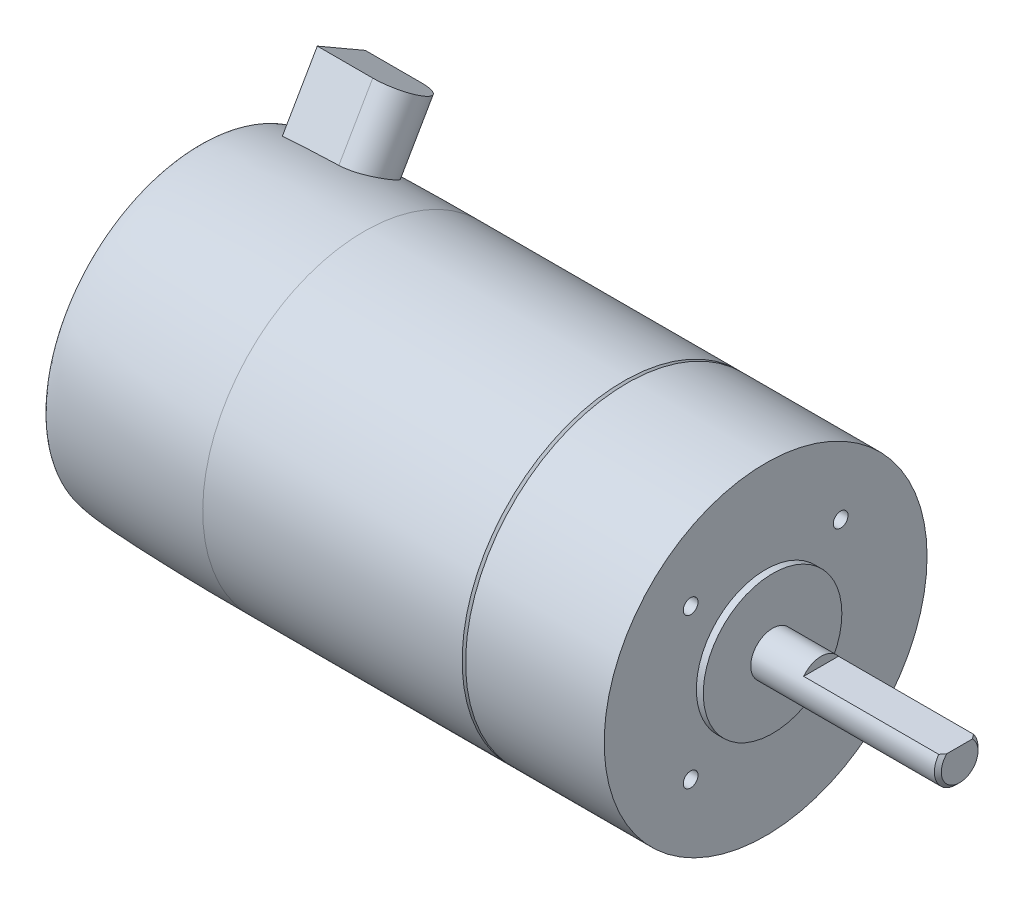
SolidWorks part; units mm, degrees
note: '?' marks a value the reader was unsure of.
material "Massless"
ref_plane "Front Plane" through (0, 0, 0) normal (0, 0, 1) x (1, 0, 0)
ref_plane "Top Plane" through (0, 0, 0) normal (0, 1, 0) x (1, 0, 0)
ref_plane "Right Plane" through (0, 0, 0) normal (1, 0, 0) x (0, 0, -1)
ref_axis "X Axis" through (88.99, 0, 0) along (-1, 0, 0)
ref_axis "Y Axis" through (0, 55, 0) along (0, -1, 0)?
ref_axis "Z Axis" through (0, 0, -88.99) along (0, 0, 1)?
sketch "Sketch2" plane through (0, 0, 0) normal (0, 0, 1) x (1, 0, 0)
  line L0 (35.56, 3.365) -> (34.925, 4) construction
  line L1 (0, -29.591) -> (-103.5558, -29.591) construction
  line L2 (0, -29.591) -> (0, 29.591) construction
  line L3 (0, 29.591) -> (-25.4, 29.591) construction
  line L4 (-103.5558, -29.591) -> (-103.5558, 29.591) construction
  line L5 (35.56, 0) -> (-116.2558, 0)
  line L6 (-116.2558, 0) -> (-116.2558, 4)
  line L7 (-116.2558, -4) -> (-103.5558, -4) construction
  line L8 (-116.2558, -4) -> (-116.2558, 4) construction
  line L9 (-116.2558, 4) -> (-103.5558, 4) construction
  line L10 (-103.5558, -4) -> (-103.5558, 4) construction
  line L11 (-116.2558, 4) -> (-103.5558, 4)
  line L12 (-103.5558, 4) -> (-103.5558, 29.591)
  line L13 (1.27, -12.7) -> (0, -12.7) construction
  line L14 (1.27, -12.7) -> (1.27, 12.7) construction
  line L15 (1.27, 12.7) -> (0, 12.7) construction
  line L16 (0, -12.7) -> (0, 12.7) construction
  line L17 (-103.5558, 29.591) -> (-26.035, 29.591)
  line L19 (35.56, -4) -> (1.27, -4) construction
  line L20 (35.56, -4) -> (35.56, 3.365) construction
  line L21 (34.925, 4) -> (1.27, 4) construction
  line L22 (1.27, -4) -> (1.27, 4) construction
  line L23 (0, 12.7) -> (1.27, 12.7)
  line L24 (1.27, 12.7) -> (1.27, 4)
  line L25 (1.27, 4) -> (34.925, 4)
  line L26 (34.925, 4) -> (35.56, 3.365)
  line L27 (35.56, 3.365) -> (35.56, 0)
  line L28 (0, 29.591) -> (0, 12.7)
  line L29 (-26.035, 29.591) -> (-25.4, 28.956)
  line L30 (-25.4, 28.956) -> (-25.4, 29.591)
  line L31 (-25.4, 29.591) -> (-26.035, 29.591) construction
  line L32 (-26.035, 29.591) -> (-103.5558, 29.591) construction
  line L33 (-26.035, 29.591) -> (-25.4, 29.591) construction
  line L34 (-25.4, 29.591) -> (0, 29.591)
  point P0 (0, 0)
  point P10 (0, 0)
  point P16 (0, 0)
  point P21 (35.56, 4)
  dimension "D1" = 103.5558
  dimension "D2" = 59.182
  dimension "D3" = 8
  dimension "D4" = 12.7
  dimension "D5" = 1.27
  dimension "D6" = 25.4
  dimension "D7" = 35.56
  dimension "D8" = 8
  dimension "D9" = 45
  dimension "D10" = 0.635
  dimension "D12" = 25.4
  dimension "D13" = 4
revolve "Revolve1" add sketch "Sketch2" angle 360 about axis through (88.99, 0, 0) along (-1, 0, 0)
fillet "Fillet1" radius 1.27 1 edges at (-103.5558, 0, -29.591)
sketch "Sketch3" plane through (35.56, 0, 0) normal (1, 0, 0) x (0, 0, -1)
  line L1 (-3.1906, 2.4125) -> (3.1906, 2.4125)
  line L2 (-3.1906, 2.4125) -> (-3.1906, 5.5875)
  line L3 (-3.1906, 5.5875) -> (3.1906, 5.5875)
  line L4 (3.1906, 2.4125) -> (3.1906, 5.5875)
  line L5 (0, 5.5875) -> (0, 2.4125) construction
  line L6 (-3.1906, 4) -> (3.1906, 4) construction
  circle A0 centre (0, 0) radius 4 construction
  point P0 (0, 4)
  dimension "D1" = 3.175
extrude "Cut-Extrude1" cut sketch "Sketch3" against normal blind 25.4
sketch "Sketch4" plane through (0, 0, 0) normal (1, 0, 0) x (0, 0, -1)
  line L0 (0, 0) -> (0, 19.4437) construction
  line L3 (0, 0) -> (19.4437, 0) construction
  line L4 (0, 0) -> (13.7488, 13.7488) construction
  circle A0 centre (0, 0) radius 19.4437 construction
  point P25 (13.7488, 13.7488)
  point P29 (13.7488, -13.7488)
  point P30 (-13.7488, -13.7488)
  point P31 (-13.7488, 13.7488)
  dimension "D1" = 38.8874
  dimension "D2" = 45
  dimension "D3" = 19.4437
  dimension "D4" = 4
hole_wizard "#6-32 Tapped Hole2" positions "Sketch4" profile "Sketch8" tap size "#6-32" standard "ANSI Inch"
sketch "Sketch8" plane through (0, 13.7488, 13.7488) normal (0, 1, 0) x (0, 0, -1)
  line L0 (0, 0) -> (0, 8.8127)
  line L1 (0, 8.8127) -> (1.3525, 8)
  line L2 (1.3525, 8) -> (1.3525, 0)
  line L5 (1.3525, 0) -> (0, 0)
  line L10 (0, 8.8127) -> (-1.3526, 8) construction
  line L11 (0, -6.35) -> (0, 107.95) construction
  dimension "Tap Drill Dia." = 2.7051
  dimension "Tap Drill Depth" = 8
  dimension "Drill Angle" = 118
cosmetic thread "Hole Thread3" parameters "D1"=7.112, "D2"=3.5052
cosmetic thread "Hole Thread12" parameters "D1"=7.112, "D2"=3.5052
cosmetic thread "Hole Thread13" parameters "D1"=7.112, "D2"=3.5052
cosmetic thread "Hole Thread14" parameters "D1"=7.112, "D2"=3.5052
sketch "Sketch6" plane through (-103.5558, 0, 0) normal (-1, 0, 0) x (0, 0, 1)
  line L2 (16.256, 0) -> (-16.256, 0) construction
  line L3 (-11.5062, -19.9293) -> (11.5062, 19.9293) construction
  circle A0 centre (0, 0) radius 16.256 construction
  circle A1 centre (0, 0) radius 23.0124 construction
  point P60 (0, 0)
  point P77 (0, 0)
  point P82 (11.5062, 19.9293)
  point P83 (8.128, 14.0781)
  point P85 (-8.128, -14.0781)
  point P89 (-11.5062, -19.9293)
  dimension "D1" = 32.512
  dimension "D2" = 46.0248
  dimension "D3" = 60
hole_wizard "#6-32 Tapped Hole1" positions "Sketch6" profile "Sketch7" tap size "#6-32" standard "ANSI Inch"
sketch "Sketch7" plane through (-103.5558, -19.9293, -11.5062) normal (0, 1, 0) x (0, 0, 1)
  line L0 (0, 0) -> (0, 10.2107)
  line L1 (0, 10.2107) -> (1.3525, 9.398)
  line L2 (1.3525, 9.398) -> (1.3525, 0)
  line L5 (1.3525, 0) -> (0, 0)
  line L10 (0, 10.2107) -> (-1.3526, 9.398) construction
  line L11 (0, -6.35) -> (0, 107.95) construction
  dimension "Tap Drill Dia." = 2.7051
  dimension "Tap Drill Depth" = 9.398
  dimension "Drill Angle" = 118
cosmetic thread "Hole Thread2" parameters "D1"=7.112, "D2"=3.5052
cosmetic thread "Hole Thread15" parameters "D1"=7.112, "D2"=3.5052
cosmetic thread "Hole Thread16" parameters "D1"=7.112, "D2"=3.5052
cosmetic thread "Hole Thread17" parameters "D1"=7.112, "D2"=3.5052
sketch "Sketch11" plane through (-103.5558, 0, 0) normal (-1, 0, 0) x (0, 0, 1)
  point P0 (-16.256, 0)
  point P3 (16.256, 0)
hole_wizard "#4-40 Tapped Hole1" [suppressed] positions "Sketch11" profile "Sketch10" tap size "#4-40" standard "ANSI Inch"
sketch "Sketch10" plane through (-103.5558, 0, -16.256) normal (0, 1, 0) x (0, 0, 1)
  line L0 (0, 0) -> (0, 8.2992)
  line L1 (0, 8.2992) -> (1.1303, 7.62)
  line L2 (1.1303, 7.62) -> (1.1303, 0)
  line L5 (1.1303, 0) -> (0, 0)
  line L10 (0, 8.2992) -> (-1.1303, 7.62) construction
  line L11 (0, -6.35) -> (0, 107.95) construction
  dimension "Tap Drill Dia." = 2.2606
  dimension "Tap Drill Depth" = 7.62
  dimension "Drill Angle" = 118
cosmetic thread "Hole Thread4" [suppressed] parameters "D1"=5.588, "D2"=2.8448
cosmetic thread "Hole Thread5" [suppressed] parameters "D1"=5.588, "D2"=2.8448
pattern_circular "CirPattern1" count 4 every 90 about axis through (88.99, 0, 0) along (-1, 0, 0) skipping 1, 2, 3 of "#6-32 Tapped Hole1", "#6-32 Tapped Hole2"
cosmetic thread "Hole Thread6" parameters "D1"=7.112, "D2"=3.5052
cosmetic thread "Hole Thread7" parameters "D1"=7.112, "D2"=3.5052
cosmetic thread "Hole Thread8" parameters "D1"=7.112, "D2"=3.5052
cosmetic thread "Hole Thread9" parameters "D1"=7.112, "D2"=3.5052
cosmetic thread "Hole Thread10" parameters "D1"=7.112, "D2"=3.5052
cosmetic thread "Hole Thread11" parameters "D1"=7.112, "D2"=3.5052
ref_plane "Lead Plane" through (0, 0, 0) normal (0, 0.866, -0.5) x (-1, 0, 0)
sketch "Sketch12" plane through (0, 0, 0) normal (0, 0.866, -0.5) x (1, 0, 0)
  line L0 (-103.5558, 29.591) -> (-103.5558, -29.591) construction
  line L1 (-98.4758, -5.08) -> (-88.3158, -5.08)
  line L2 (-98.4758, -5.08) -> (-98.4758, 5.08)
  line L3 (-98.4758, 5.08) -> (-88.3158, 5.08)
  line L6 (-98.4758, 0) -> (-83.2358, 0) construction
  arc A0 (-88.3158, -5.08) -> (-88.3158, 5.08) centre (-88.3158, 0) ccw
  dimension "D1" = 5.08
  dimension "D2" = 10.16
  dimension "D3" = 10.16
extrude "Boss-Extrude1" add sketch "Sketch12" along normal blind 41.402
